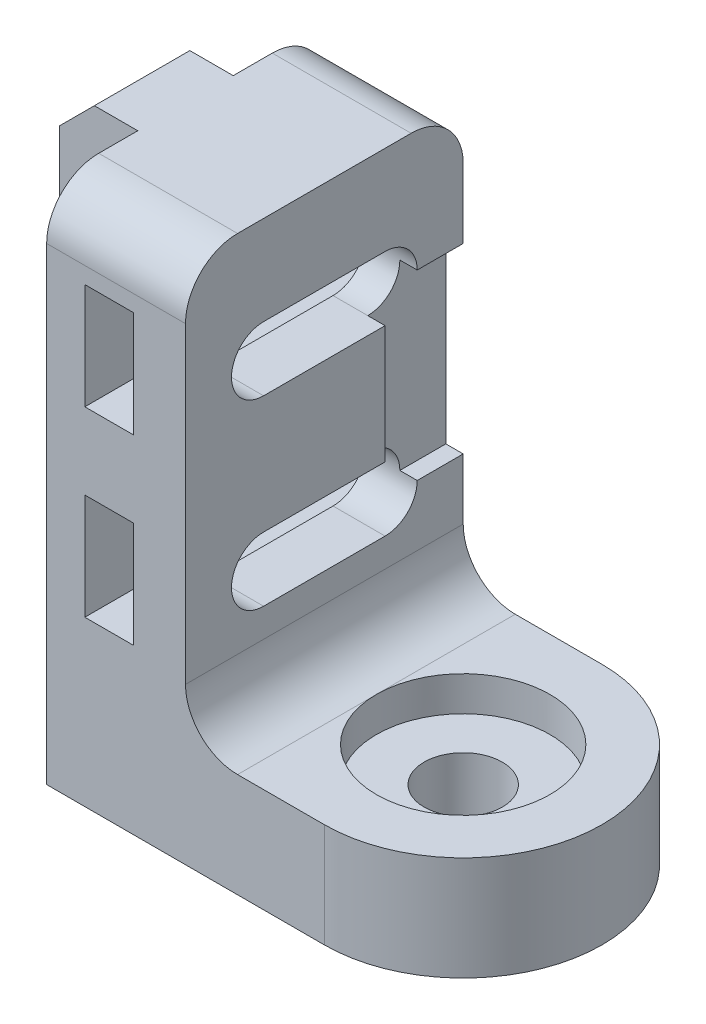
SolidWorks part; units mm, degrees
ref_plane "Front Plane" through (0, 0, 0) normal (0, 0, 1) x (1, 0, 0)
ref_plane "Top Plane" through (0, 0, 0) normal (0, 1, 0) x (1, 0, 0)
ref_plane "Right Plane" through (0, 0, 0) normal (1, 0, 0) x (0, 0, -1)
sketch "Sketch1" plane through (0, 0, 0) normal (1, 0, 0) x (0, 0, -1)
  line L0 (-32.8466, 27.9115) -> (-32.8466, -2.0885)
  line L5 (-32.8466, -2.0885) -> (-48.8466, -2.0885)
  line L6 (-48.8466, -2.0885) -> (-48.8466, 27.9115)
  line L8 (-48.8466, 27.9115) -> (-32.8466, 27.9115)
  dimension "D9" = 16
  dimension "D10" = 30
extrude "Boss-Extrude1" add sketch "Sketch1" along normal blind 8
sketch "Sketch2" plane through (0, 0, 0) normal (-1, 0, 0) x (0, 0, 1)
  line L0 (40.8466, 5.9115) -> (40.8466, 12.9115) construction
  line L1 (48.8466, 27.9115) -> (48.8466, -2.0885) construction
  line L3 (38.0966, 27.9115) -> (43.5966, 27.9115)
  line L4 (38.0966, 27.9115) -> (38.0966, -2.0885)
  line L5 (38.0966, -2.0885) -> (43.5966, -2.0885)
  line L6 (43.5966, 27.9115) -> (43.5966, -2.0885)
  line L7 (38.0966, 27.9115) -> (43.5966, -2.0885) construction
  line L8 (38.0966, -2.0885) -> (43.5966, 27.9115) construction
  line L9 (48.8466, -2.0885) -> (32.8466, -2.0885) construction
  line L10 (32.8466, 27.9115) -> (48.8466, 27.9115) construction
  point P5 (40.8466, 12.9115)
  dimension "D1" = 5.5
  dimension "D3" = 8
extrude "Boss-Extrude2" add sketch "Sketch2" along normal blind 4.5
chamfer "Chamfer1" distance 2 angle 45 2 edges at (-4.5, -2.0885, 40.8466) (-4.5, 27.9115, 40.8466)
sketch "Sketch6" plane through (0, -2.0885, 0) normal (0, -1, 0) x (1, 0, 0)
  line L0 (8, 48.8466) -> (16, 48.8466)
  line L2 (16, 32.8466) -> (8, 32.8466)
  line L3 (8, 32.8466) -> (8, 48.8466)
  arc A0 (16, 32.8466) -> (16, 48.8466) centre (16, 40.8466) ccw
  circle A1 centre (16, 40.8466) radius 2.25
  dimension "D2" = 4.5
  dimension "D1" = 8
extrude "Boss-Extrude3" add sketch "Sketch6" against normal blind 6
fillet "Fillet6" radius 3 1 edges at (8, 3.9115, 40.8466)
sketch "Sketch7" plane through (8, 0, 0) normal (1, 0, 0) x (0, 0, -1)
  line L0 (-32.8466, 6.9115) -> (-32.8466, 27.9115) construction
  line L1 (-48.8466, 23.9615) -> (-32.8466, 23.9615)
  line L2 (-48.8466, 23.9615) -> (-48.8466, 17.8615)
  line L3 (-48.8466, 17.8615) -> (-32.8466, 17.8615)
  line L4 (-32.8466, 23.9615) -> (-32.8466, 17.8615)
  line L5 (-48.8466, 27.9115) -> (-48.8466, 6.9115) construction
  line L7 (-48.8466, 13.4615) -> (-32.8466, 13.4615)
  line L8 (-48.8466, 13.4615) -> (-48.8466, 7.3615)
  line L9 (-48.8466, 7.3615) -> (-32.8466, 7.3615)
  line L10 (-32.8466, 13.4615) -> (-32.8466, 7.3615)
  point P6 (-48.8466, 20.9115)
  dimension "D1" = 10.5
  dimension "D2" = 6.1
  dimension "D3" = 7
extrude "Cut-Extrude1" cut sketch "Sketch7" against normal blind 2.8 from offset 3 offset against normal yes
sketch "Sketch8" plane through (8, 0, 0) normal (1, 0, 0) x (0, 0, -1)
  line L0 (-44.3466, 20.9115) -> (-37.3466, 20.9115) construction
  line L1 (-44.3466, 22.7615) -> (-37.3466, 22.7615)
  line L2 (-44.3466, 19.0615) -> (-37.3466, 19.0615)
  line L3 (-44.3466, 10.4115) -> (-37.3466, 10.4115) construction
  line L4 (-44.3466, 12.2615) -> (-37.3466, 12.2615)
  line L5 (-44.3466, 8.5615) -> (-37.3466, 8.5615)
  line L6 (-32.8466, 27.9115) -> (-48.8466, 27.9115) construction
  arc A0 (-44.3466, 22.7615) -> (-44.3466, 19.0615) centre (-44.3466, 20.9115) ccw
  arc A1 (-37.3466, 19.0615) -> (-37.3466, 22.7615) centre (-37.3466, 20.9115) ccw
  arc A2 (-44.3466, 12.2615) -> (-44.3466, 8.5615) centre (-44.3466, 10.4115) ccw
  arc A3 (-37.3466, 8.5615) -> (-37.3466, 12.2615) centre (-37.3466, 10.4115) ccw
  point P2 (-40.8466, 20.9115)
  point P7 (-40.8466, 10.4115)
  point P19 (-40.8466, 27.9115)
  dimension "D4" = 1.85
  dimension "D1" = 10.5
  dimension "D2" = 7
  dimension "D3" = 7
extrude "Cut-Extrude2" cut sketch "Sketch8" against normal blind 5
sketch "Sketch9" plane through (8, 0, 0) normal (1, 0, 0) x (0, 0, -1)
  line L0 (-32.8466, 6.9115) -> (-32.8466, 27.9115) construction
  line L1 (-32.8466, 20.9115) -> (-37.3466, 20.9115)
  line L2 (-32.8466, 20.9115) -> (-32.8466, 10.4115)
  line L3 (-32.8466, 10.4115) -> (-37.3466, 10.4115)
  line L4 (-37.3466, 20.9115) -> (-37.3466, 10.4115)
  point P6 (-37.3466, 10.4115)
  point P8 (-37.3466, 20.9115)
extrude "Cut-Extrude3" cut sketch "Sketch9" against normal blind 1
sketch "Sketch10" plane through (0, 3.9115, 0) normal (0, 1, 0) x (1, 0, 0)
  circle A0 centre (16, -40.8466) radius 5
extrude "Cut-Extrude4" cut sketch "Sketch10" against normal blind 2
fillet "Fillet7" radius 3 2 edges at (4, 27.9115, 32.8466) (4, 27.9115, 48.8466)
